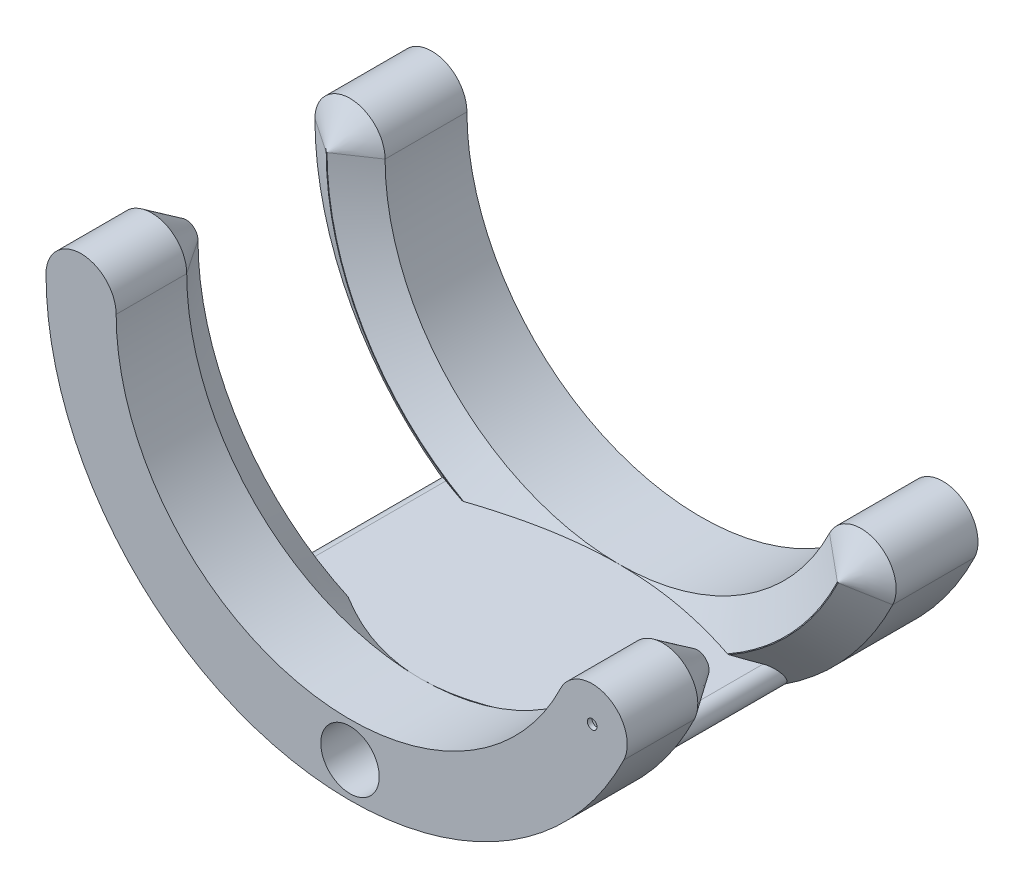
SolidWorks part; units mm, degrees
ref_plane "Front Plane" through (0, 0, 0) normal (0, 0, 1) x (1, 0, 0)
ref_plane "Top Plane" through (0, 0, 0) normal (0, 1, 0) x (1, 0, 0)
ref_plane "Right Plane" through (0, 0, 0) normal (1, 0, 0) x (0, 0, -1)
sketch "Sketch1" plane through (0, 0, 0) normal (0, 0, 1) x (1, 0, 0)
  line L0 (-48.3017, 0) -> (-4.3076, 0) construction
  line L1 (-26.3046, -12.7) -> (-26.3046, -20.32) construction
  arc A1 (3.431, -1.6565) -> (-3.431, 1.6565) centre (0, 0) ccw
  arc A2 (-51.7046, 12.7) -> (-3.431, 1.6565) centre (-26.3046, 12.7) ccw
  arc A3 (-59.3246, 12.7) -> (3.431, -1.6565) centre (-26.3046, 12.7) ccw
  circle A4 centre (-26.3046, -16.51) radius 3.175
  arc A5 (-59.3246, 12.7) -> (-51.7046, 12.7) centre (-55.5146, 12.7) cw
  point P11 (-26.3046, -12.7)
  point P13 (-26.3046, 0)
  point P15 (-26.3046, -20.32)
  dimension "D2" = 6.35
  dimension "D3" = 33.02
  dimension "D6" = 25.4
  dimension "D1" = 12.7
  dimension "D4" = 90
extrude "Boss-Extrude1" add sketch "Sketch1" along normal blind 38.1
sketch "Sketch2" plane through (0, 0, 38.1) normal (0, 0, 1) x (1, 0, 0)
  circle A0 centre (0, 0) radius 0.5241
extrude "Cut-Extrude1" cut sketch "Sketch2" against normal blind 0.508
ref_plane "Plane1" through (0, 0, 19.05) normal (0, 0, 1) x (1, 0, 0)
mirror "Mirror1" about plane through (0, 0, 19.05) normal (0, 0, 1) of "Cut-Extrude1"
sketch "Sketch4" plane through (0, 0, 0) normal (1, 0, 0) x (0, 0, -1)
  line L0 (0, 16.51) -> (-38.1, 16.51) construction
  line L1 (-26.67, 16.51) -> (-11.43, 16.51)
  line L2 (-26.67, 16.51) -> (-26.67, -12.7)
  line L3 (-26.67, -12.7) -> (-11.43, -12.7)
  line L4 (-11.43, 16.51) -> (-11.43, -12.7)
  line L6 (-38.1, -12.7) -> (0, -12.7) construction
  point P4 (-19.05, 16.51)
  point P5 (-19.05, 16.51)
  point P6 (0, 0)
  dimension "D1" = 15.24
extrude "Cut-Extrude2" cut sketch "Sketch4" against normal through all and the other way through all contours L2 L3 L4 L1
chamfer "Chamfer1" distance 2.54 angle 56 12 edges at (-56.1961, -1.3292, 26.67) (-0.2945, -7.6419, 26.67) (-55.5146, 16.51, 26.67) (1.6565, 3.431, 26.67) (-44.2652, -5.2605, 26.67) (-12.8018, -8.8135, 26.67) (-56.1961, -1.3292, 11.43) (-0.2945, -7.6419, 11.43) (-55.5146, 16.51, 11.43) (1.6565, 3.431, 11.43) (-44.2652, -5.2605, 11.43) (-12.8018, -8.8135, 11.43) first distance on face at (-48.2075, -0.6949, 26.67) first distance on face at (-6.7987, -6.4311, 26.67) first distance on face at (-28.7262, -5.0194, 19.05) first distance on face at (-55.5146, 14.605, 5.715) first distance on face at (0.8283, 1.7155, 5.715) first distance on face at (-28.8343, -2.3556, 6.858)
fillet "Fillet1" radius 1.27 2 edges at (-5.2058, -12.7, 19.6629) (-47.4035, -12.7, 19.6629)
